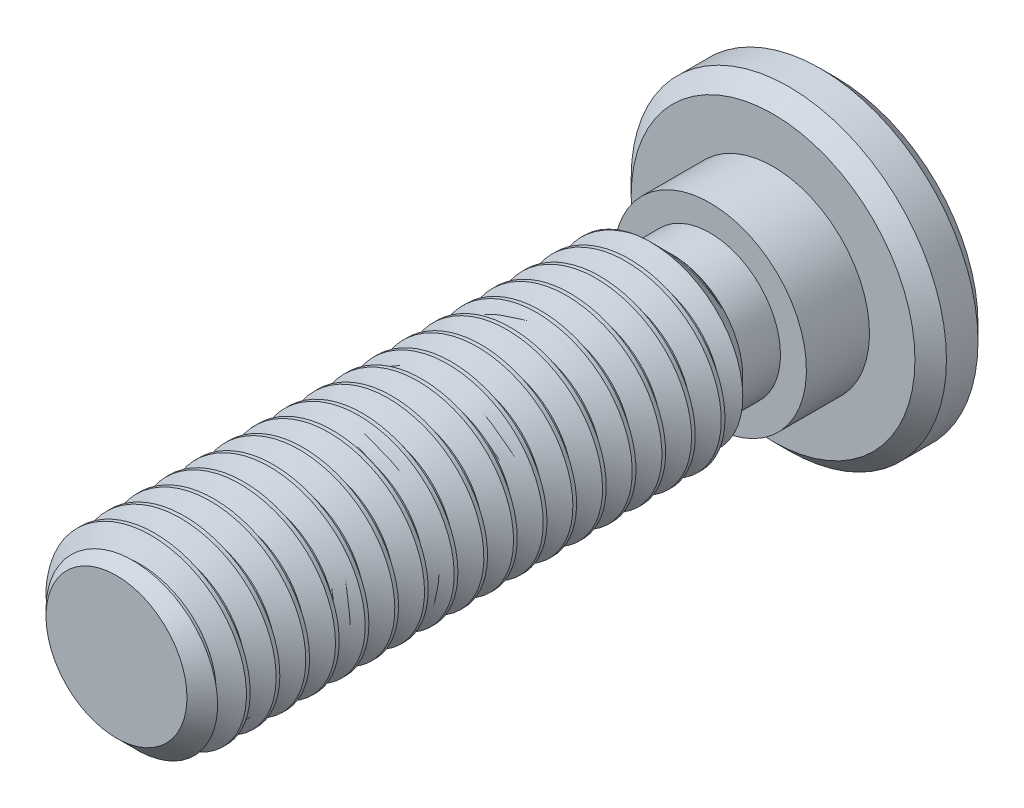
SolidWorks part; units mm, degrees
other "DetailItem1"
ref_plane "Front Plane" through (0, 0, 0) normal (0, 0, 1) x (1, 0, 0)
ref_plane "Top Plane" through (0, 0, 0) normal (0, 1, 0) x (1, 0, 0)
ref_plane "Right Plane" through (0, 0, 0) normal (1, 0, 0) x (0, 0, -1)
sketch "Sketch1" plane through (0, 0, 0) normal (1, 0, 0) x (0, 0, -1)
  line L0 (0, 0) -> (-17.7, 0) construction
  line L1 (0, 0) -> (1.7, 0) construction
  line L2 (1.7, 4.25) -> (1.7, -4.25) construction
  line L3 (-17.7, 2.5) -> (-17.7, -2.5) construction
  line L4 (0, 2.6) -> (0, -2.6) construction
  line L5 (-17.7, 2.5) -> (-16.9, 2.5) construction
  line L6 (1.7, 1.5) -> (1.7, -1.5) construction
  line L7 (0, 2.6) -> (-1.7, 2.6) construction
  line L8 (-1.7, 2.6) -> (-1.7, 1.9) construction
  line L9 (-1.7, 1.9) -> (-2.716, 1.9) construction
  line L10 (-2.716, 1.9) -> (-3.316, 2.5) construction
  point P2 (-14.9, -2.5)
  point P4 (-1.7, 0)
  point P8 (1.7, 0)
  point P11 (-17.7, 0)
  point P14 (0, 0)
  point P19 (1.7, 0)
  dimension "Thread Diameter" = 5
  dimension "Head Diameter" = 8.5
  dimension "Head Height" = 1.7
  dimension "Shoulder Diameter" = 5.2
  dimension "Shoulder Length" = 1.7
  dimension "Thread Pitch" = 0.8
  dimension "Drive Size" = 3
  dimension "D1" = 2.8
  dimension "D2" = 45
  dimension "Undercut Length" = 1.016
  dimension "D3" = 3.8
  dimension "Length" = 16
sketch "Sketch13" plane through (0, 0, 0) normal (1, 0, 0) x (0, 0, -1)
  line L0 (1.7, 4.25) -> (0, 4.25)
  line L1 (0, 4.25) -> (0, 2.6)
  line L3 (-17.7, 2.5) -> (-17.7, 0)
  line L4 (-17.7, 0) -> (1.7, 0)
  line L5 (1.7, 0) -> (1.7, 4.25)
  line L6 (-2.716, 1.9) -> (-3.316, 2.5) construction
  line L7 (-1.7, 1.9) -> (-2.716, 1.9) construction
  line L8 (-1.7, 2.6) -> (-1.7, 1.9) construction
  line L9 (0, 2.6) -> (-1.7, 2.6) construction
  line L10 (-2.716, 1.9) -> (-3.316, 2.5)
  line L11 (-1.7, 1.9) -> (-2.716, 1.9)
  line L12 (-1.7, 2.6) -> (-1.7, 1.9)
  line L13 (0, 2.6) -> (-1.7, 2.6)
  line L14 (-3.316, 2.5) -> (-17.7, 2.5)
revolve "Revolve1" add sketch "Sketch13" angle 360 about L4
sketch "Sketch2" plane through (0, 0, 17.7) normal (0, 0, 1) x (1, 0, 0)
  circle A2 centre (0, 0) radius 2.5
chamfer "Chamfer2" distance 0.6 angle 45 1 edges at (0, -2.5, 17.7)
sketch "Sketch3" plane through (0, 0, 0) normal (1, 0, 0) x (0, 0, -1)
  line L0 (-17.65, 2.5866) -> (-18.45, 2.5866) construction
  line L1 (-18.45, 2.5866) -> (-18.05, 1.8938) construction
  line L2 (-18.05, 1.8938) -> (-17.65, 2.5866) construction
  line L4 (-17.7, 2.5) -> (-18.4, 2.5) construction
  line L5 (-18.05, 2.5866) -> (-18.05, 2.5) construction
  line L6 (-18.425, 2.5433) -> (-17.675, 2.5433)
  line L7 (-17.675, 2.5433) -> (-18.425, 2.5433) construction
  line L8 (-18, 1.9804) -> (-18.1, 1.9804) construction
  line L9 (-18.05, 1.9804) -> (-18.05, 1.8938) construction
  line L10 (-17.675, 2.5433) -> (-18, 1.9804)
  line L11 (-18, 1.9804) -> (-18.1, 1.9804)
  line L12 (-18.1, 1.9804) -> (-18.425, 2.5433)
  point P16 (-18.05, 2.5433)
  dimension "D1" = 0.8
  dimension "D2" = 0.1
sketch "Sketch7" plane through (0, 0, -1.7) normal (0, 0, -1) x (-1, 0, 0)
  line L1 (0, 1.7321) -> (-1.5, 0.866)
  line L2 (-1.5, 0.866) -> (-1.5, -0.866)
  line L3 (-1.5, -0.866) -> (0, -1.7321)
  line L4 (0, -1.7321) -> (1.5, -0.866)
  line L5 (1.5, -0.866) -> (1.5, 0.866)
  line L6 (1.5, 0.866) -> (0, 1.7321)
  circle A0 centre (0, 0) radius 1.5 construction
extrude "Cut-Extrude1" cut sketch "Sketch7" against normal blind 2.25
chamfer "Chamfer1" distance 0.425 angle 45 2 edges at (0, -4.25, -1.7) (0, -4.25, 0)
sketch "Sketch8" plane through (0, 0, -1.7) normal (0, 0, -1) x (-1, 0, 0)
  circle A0 centre (0, 0) radius 1.7321
extrude "Cut-Extrude2" cut sketch "Sketch8" against normal through all draft 45
curve "Helix/Spiral1" pitch 0.8 height 15.9 turns 19.875 parameters "pitch"=0.8
sweep "Cut-Sweep1" cut profiles "Sketch3" path "Helix/Spiral1"
equation "\"D3@Helix/Spiral1\"=\"Length@Sketch1\"-.1"
equation "\"D1@Cut-Extrude1\" = \"Drive Size@Sketch1\" * .75"
equation "\"D1@Chamfer1\" = \"Head Diameter@Sketch1\" * .05"
equation "\"D1@Chamfer2\"=\"pitch@Helix/Spiral1\"*.750"
equation "\"D1@Sketch3\" = \"Thread Pitch@Sketch1\""
equation "\"D2@Sketch3\"=\"D1@Sketch3\"/ 1/8"
equation "\"pitch@Helix/Spiral1\" = \"Thread Pitch@Sketch1\""
equation "\"D1@Sketch1\" = \"Thread Pitch@Sketch1\" * 3.5"
equation "\"D3@Sketch1\"=\"Thread Diameter@Sketch1\"-(\"Thread Pitch@Sketch1\"*1.5)"
